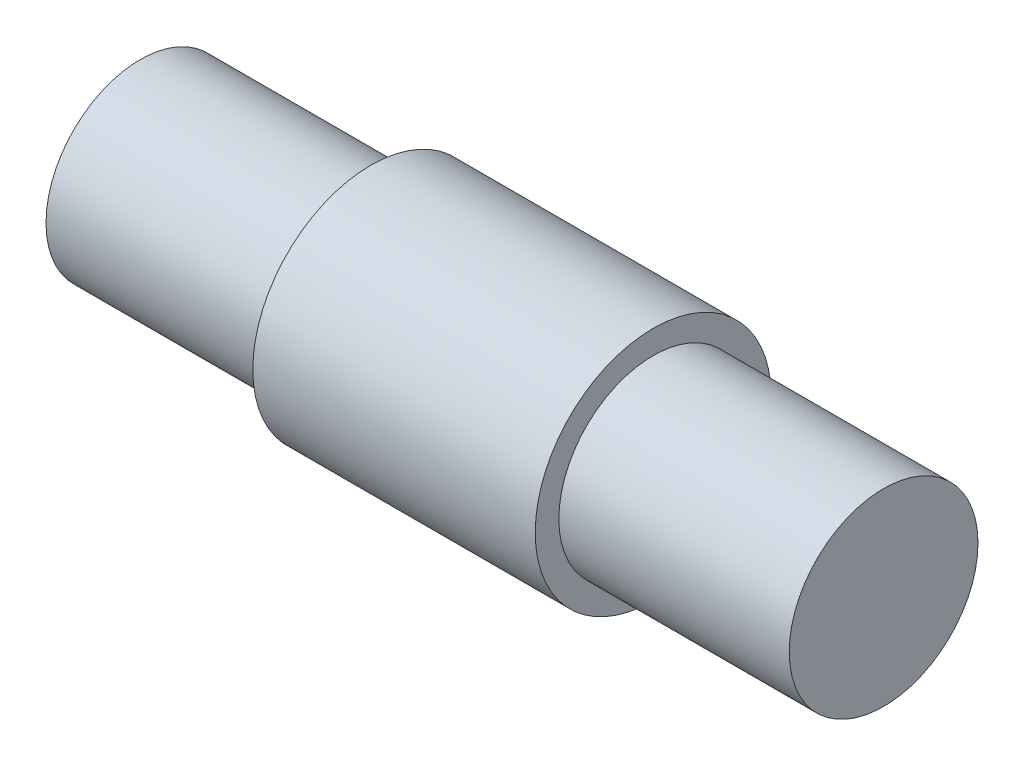
SolidWorks part; units mm, degrees
material "Alloy Steel"
ref_plane "Front Plane" through (0, 0, 0) normal (0, 0, 1) x (1, 0, 0)
ref_plane "Top Plane" through (0, 0, 0) normal (0, 1, 0) x (1, 0, 0)
ref_plane "Right Plane" through (0, 0, 0) normal (1, 0, 0) x (0, 0, -1)
sketch "Sketch1" plane through (0, 0, 0) normal (0, 0, 1) x (1, 0, 0)
  line L0 (-76.4565, 0) -> (100.0218, 0) construction
  line L1 (-12.5, 0) -> (-12.5, 3.175)
  line L2 (-12.5, 3.175) -> (-4.75, 3.175)
  line L3 (-4.75, 3.175) -> (-4.75, 3.9688)
  line L4 (-4.75, 3.9688) -> (4.75, 3.9688)
  line L5 (4.75, 3.9688) -> (4.75, 3.175)
  line L6 (4.75, 3.175) -> (12.5, 3.175)
  line L7 (12.5, 3.175) -> (12.5, 0)
  line L8 (12.5, 0) -> (-12.5, 0)
  dimension "D1" = 7.75
  dimension "D2" = 25
  dimension "D3" = 7.9375
  dimension "D4" = 6.35
revolve "Revolve1" add sketch "Sketch1" angle 360 about L0
